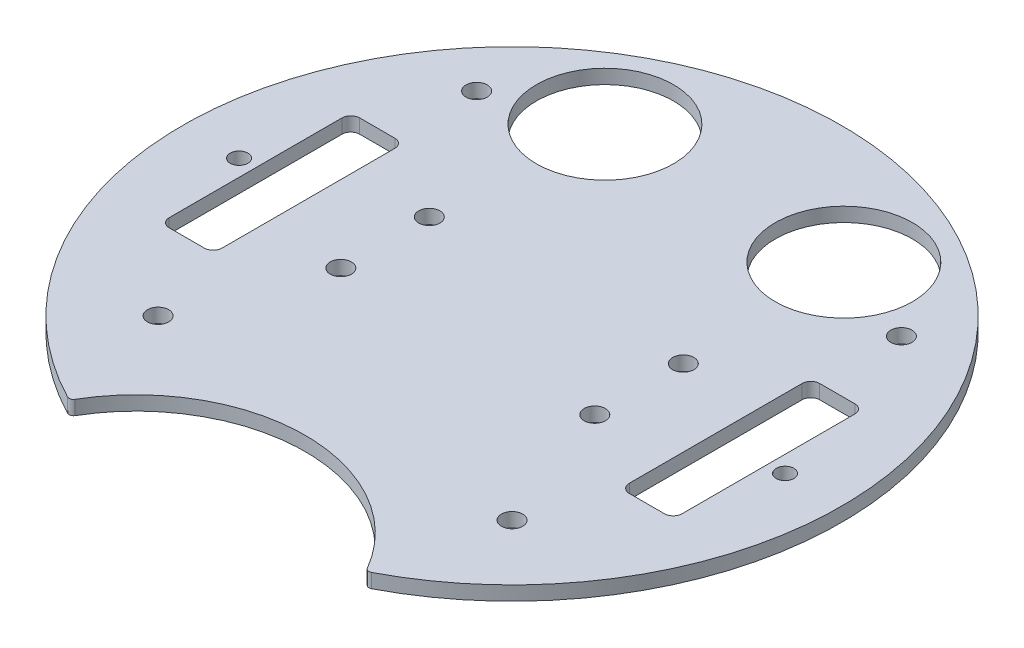
SolidWorks part; units mm, degrees
material "Plain Carbon Steel"
ref_plane "Front Plane" through (0, 0, 0) normal (0, 0, 1) x (1, 0, 0)
ref_plane "Top Plane" through (0, 0, 0) normal (0, 1, 0) x (1, 0, 0)
ref_plane "Right Plane" through (0, 0, 0) normal (1, 0, 0) x (0, 0, -1)
sketch "Sketch1" plane through (0, 0, 0) normal (0, 1, 0) x (1, 0, 0)
  line L1 (0, -85) -> (0, 0) construction
  arc A0 (34.3603, -66.1031) -> (-34.3603, -66.1031) centre (0, 0) ccw
  arc A1 (33.0354, -65.7199) -> (-33.0354, -65.7199) centre (0, -85) ccw
  arc A2 (34.3603, -66.1031) -> (33.0354, -65.7199) centre (33.8991, -65.2158) cw
  arc A3 (-33.0354, -65.7199) -> (-34.3603, -66.1031) centre (-33.8991, -65.2158) cw
  point P10 (0, 0)
  point P11 (-32.963, -65.5963)
  dimension "D1" = 149
  dimension "D2" = 76.5
  dimension "D4" = 1
  dimension "D3" = 85
extrude "Boss-Extrude1" add sketch "Sketch1" along normal blind 3.2
sketch "solenoid placement" plane through (0, 3.2, 0) normal (0, 1, 0) x (1, 0, 0)
  line L0 (0, 0) -> (0, -36) construction
  line L1 (0, -36) -> (0, -46.75) construction
  line L2 (-19, -36) -> (19, -36)
  line L3 (-19, -36) -> (-19, 28)
  line L4 (-19, 28) -> (19, 28)
  line L5 (19, -36) -> (19, 28)
  circle A1 centre (0, 0) radius 74.5 construction
  arc A2 (34.3603, -66.1031) -> (-34.3603, -66.1031) centre (0, 0) ccw construction
  arc A3 (33.0354, -65.7199) -> (-33.0354, -65.7199) centre (0, -85) ccw construction
  dimension "D1" = 64
  dimension "D2" = 36
  dimension "D4" = 38
sketch "Sketch2" plane through (0, 3.2, 0) normal (0, 1, 0) x (1, 0, 0)
  line L1 (-57.07, 20.6344) -> (-46.91, 20.6344) construction
  line L2 (-57.07, 20.6344) -> (-57.07, -20.6344) construction
  line L3 (-57.07, -20.6344) -> (-46.91, -20.6344) construction
  line L4 (-46.91, 20.6344) -> (-46.91, -20.6344) construction
  line L8 (-57.37, -20.9344) -> (-46.61, -20.9344)
  line L9 (-46.61, 20.9344) -> (-46.61, -20.9344)
  line L10 (-57.37, 20.9344) -> (-46.61, 20.9344)
  line L11 (-57.37, 20.9344) -> (-57.37, -20.9344)
  line L12 (0, 0) -> (0, 74.5) construction
  line L13 (46.91, 20.6344) -> (46.91, -20.6344) construction
  line L14 (57.07, -20.6344) -> (46.91, -20.6344) construction
  line L15 (57.07, 20.6344) -> (57.07, -20.6344) construction
  line L16 (57.07, 20.6344) -> (46.91, 20.6344) construction
  line L17 (57.37, 20.9344) -> (57.37, -20.9344)
  line L18 (57.37, 20.9344) -> (46.61, 20.9344)
  line L19 (46.61, 20.9344) -> (46.61, -20.9344)
  line L20 (57.37, -20.9344) -> (46.61, -20.9344)
  arc A0 (34.3603, -66.1031) -> (-34.3603, -66.1031) centre (0, 0) ccw construction
extrude "Cut-Extrude1" cut sketch "Sketch2" against normal through all
sketch "Sketch3" plane through (0, 0, 0) normal (0, -1, 0) x (1, 0, 0)
  line L0 (0, 0) -> (0, -74.5) construction
  circle A0 centre (-61.7, 0) radius 2
  circle A1 centre (-28.7007, 10) radius 2.4
  circle A2 centre (-28.7007, -10) radius 2.4
  arc A3 (-34.3603, 66.1031) -> (34.3603, 66.1031) centre (0, 0) ccw construction
  circle A4 centre (28.7007, -10) radius 2.4
  circle A5 centre (28.7007, 10) radius 2.4
  circle A6 centre (61.7, 0) radius 2
  dimension "D1" = 4
  dimension "D2" = 4.8
extrude "Cut-Extrude2" cut sketch "Sketch3" against normal through all
sketch "Sketch4" plane through (0, 3.2, 0) normal (0, 1, 0) x (1, 0, 0)
  line L0 (0, 0) -> (0, 74.5) construction
  line L1 (0, 48) -> (-27, 48) construction
  circle A0 centre (-27, 48) radius 15
  arc A1 (34.3603, -66.1031) -> (-34.3603, -66.1031) centre (0, 0) ccw construction
  circle A2 centre (27, 48) radius 15
  dimension "D1" = 30
  dimension "D2" = 48
  dimension "D3" = 27
extrude "Cut-Extrude3" cut sketch "Sketch4" against normal through all
sketch "Sketch5" plane through (0, 3.2, 0) normal (0, 1, 0) x (1, 0, 0)
  line L0 (0, 0) -> (0, 74.5) construction
  line L1 (-55.9558, 21.5201) -> (-48.0242, 21.5201)
  line L2 (-57.9558, 19.5201) -> (-57.9558, -19.5201)
  line L3 (-55.9558, -21.5201) -> (-48.0242, -21.5201)
  line L4 (-46.0242, 19.5201) -> (-46.0242, -19.5201)
  line L5 (46.0242, 19.5201) -> (46.0242, -19.5201)
  line L6 (55.9558, -21.5201) -> (48.0242, -21.5201)
  line L7 (57.9558, 19.5201) -> (57.9558, -19.5201)
  line L8 (55.9558, 21.5201) -> (48.0242, 21.5201)
  arc A0 (-57.9558, -19.5201) -> (-55.9558, -21.5201) centre (-55.9558, -19.5201) ccw
  arc A1 (-48.0242, -21.5201) -> (-46.0242, -19.5201) centre (-48.0242, -19.5201) ccw
  arc A2 (-48.0242, 21.5201) -> (-46.0242, 19.5201) centre (-48.0242, 19.5201) cw
  arc A3 (-55.9558, 21.5201) -> (-57.9558, 19.5201) centre (-55.9558, 19.5201) ccw
  arc A4 (34.3603, -66.1031) -> (-34.3603, -66.1031) centre (0, 0) ccw construction
  arc A5 (55.9558, 21.5201) -> (57.9558, 19.5201) centre (55.9558, 19.5201) cw
  arc A6 (48.0242, 21.5201) -> (46.0242, 19.5201) centre (48.0242, 19.5201) ccw
  arc A7 (48.0242, -21.5201) -> (46.0242, -19.5201) centre (48.0242, -19.5201) cw
  arc A8 (57.9558, -19.5201) -> (55.9558, -21.5201) centre (55.9558, -19.5201) cw
  point P15 (-57.37, 20.9344)
  dimension "D1" = 2
extrude "Cut-Extrude4" cut sketch "Sketch5" against normal through all
sketch "Sketch6" plane through (0, 3.2, 0) normal (0, 1, 0) x (1, 0, 0)
  line L0 (0, 74.5) -> (0, -46.75) construction
  circle A0 centre (48, 40) radius 2.4
  circle A1 centre (-40, -40) radius 2.4
  arc A4 (34.3603, -66.1031) -> (-34.3603, -66.1031) centre (0, 0) ccw construction
  arc A5 (33.0354, -65.7199) -> (-33.0354, -65.7199) centre (0, -85) ccw construction
  circle A6 centre (40, -40) radius 2.4
  circle A7 centre (-48, 40) radius 2.4
  dimension "D3" = 4.8
  dimension "D1" = 40
  dimension "D2" = 40
  dimension "D4" = 48
  dimension "D5" = 40
extrude "Cut-Extrude5" cut sketch "Sketch6" against normal through all
chamfer "Chamfer1" [suppressed] distance 2 angle 41
sketch "Sketch8" plane through (0, 3.2, 0) normal (0, 1, 0) x (1, 0, 0)
  circle A0 centre (-27, 48) radius 15.5
  circle A1 centre (27, 48) radius 15.5
  dimension "D1" = 31
extrude "Cut-Extrude6" cut sketch "Sketch8" against normal through all
equation "\"smallPulleyTeeth\"= 15"
equation "\"largePulleyTeeth\"= 30"
equation "\"eighthThick\"= 2.9mm"
equation "\"sixteenthThick\" = 1.7mm"
equation "\"quarterThick\"=6.0mm"
equation "\"OD\" = 145mm"
equation "\"puckAngle\" = 60.5deg"
equation "\"puckDiam\" = 76.5mm"
equation "\"D2@Sketch1\"=\"puckDiam\""
equation "\"D1@Boss-Extrude1\"=\"eighthThick\""
equation "\"axlePress\" = 5.9mm"
equation "\"press\" = 0.2mm"
equation "\"wheelClear\" = 0.3mm"
equation "\"D1@Sketch2\"=\"wheelClear\""
equation "\"10-32clear\" = 4.8mm"
equation "\"6-32clear\" = 3.3mm"
equation "\"8-32clear\" = 4.0mm"
equation "\"wheelHeight\" = 22mm"
equation "\"D1@Sketch3\"=\"8-32clear\""
equation "\"D2@Sketch3\"=\"10-32clear\""
equation "\"D3@Sketch6\"=\"10-32clear\""
equation "\"puckDist\" = 85mm"
equation "\"4-40clear\" = 3.0mm"
equation "\"wheelWell\" = 65mm"
equation "\"D3@Sketch1\"=\"puckDist\""
